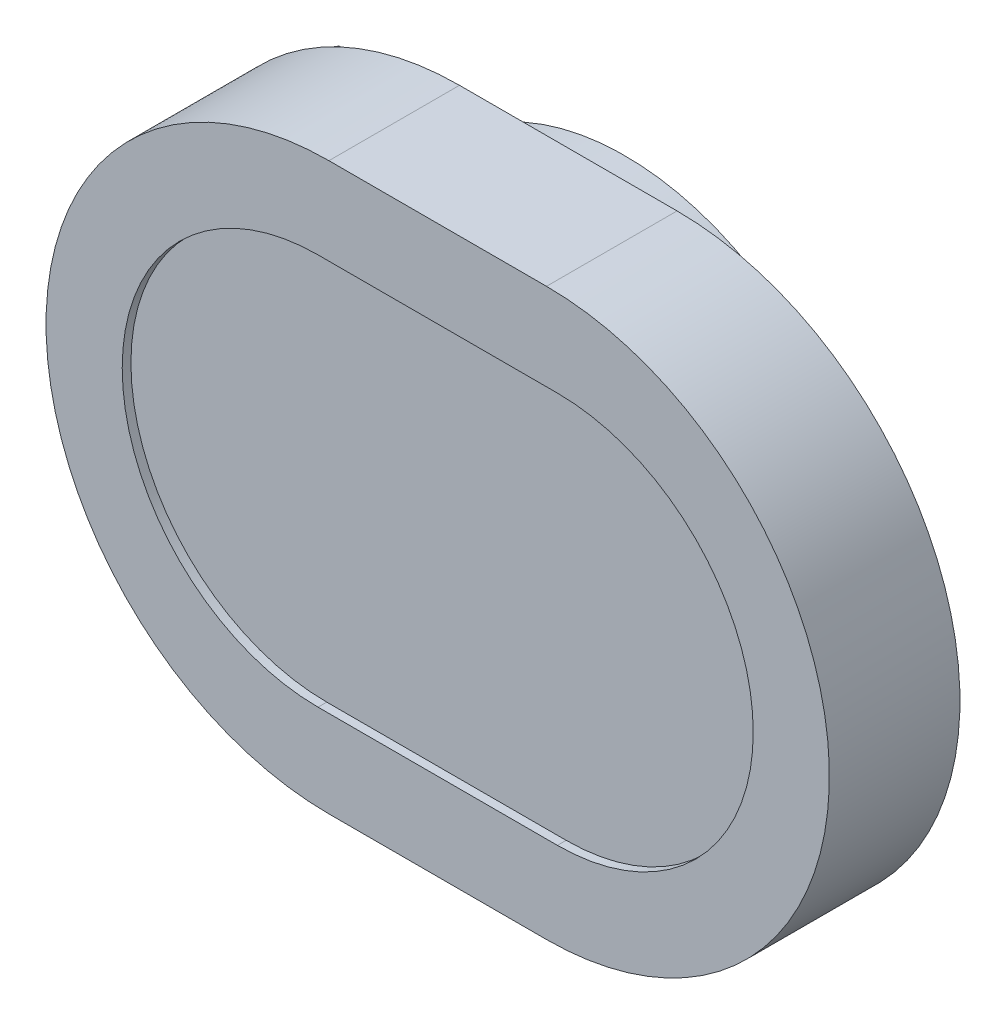
SolidWorks part; units mm, degrees
material "ABS"
ref_plane "Спереди" through (0, 0, 0) normal (0, 0, 1) x (1, 0, 0)
ref_plane "Сверху" through (0, 0, 0) normal (0, 1, 0) x (1, 0, 0)
ref_plane "Справа" through (0, 0, 0) normal (1, 0, 0) x (0, 0, -1)
ref_axis "Ось1" through (0, 0, 50) along (0, 0, -1)
sketch "Эскиз1" plane through (0, 0, 0) normal (0, 0, 1) x (1, 0, 0)
  circle A0 centre (0, 0) radius 5.7
  dimension "D1" = 11.4
extrude "Бобышка-Вытянуть1" add sketch "Эскиз1" along normal blind 1.3
sketch "Эскиз2" plane through (0, 0, 1.3) normal (0, 0, 1) x (1, 0, 0)
  line L0 (-2.5, 0) -> (2.5, 0) construction
  line L1 (-2.5, 6.5) -> (2.5, 6.5)
  line L2 (-2.5, -6.5) -> (2.5, -6.5)
  arc A0 (-2.5, 6.5) -> (-2.5, -6.5) centre (-2.5, 0) ccw
  arc A1 (2.5, -6.5) -> (2.5, 6.5) centre (2.5, 0) ccw
  point P2 (0, 0)
  point P8 (-9, 0)
  point P9 (9, 0)
  dimension "D1" = 18
  dimension "D2" = 13
extrude "Бобышка-Вытянуть2" add sketch "Эскиз2" along normal blind 2.8
sketch "Эскиз3" plane through (0, 0, 4.1) normal (0, 0, 1) x (1, 0, 0)
  line L0 (-2.75, 0) -> (2.75, 0) construction
  line L1 (-2.75, 4.5) -> (2.75, 4.5)
  line L2 (-2.75, -4.5) -> (2.75, -4.5)
  line L3 (-2.5, 0) -> (2.5, 0) construction
  line L4 (-2.5, 6.5) -> (2.5, 6.5)
  line L5 (-2.5, -6.5) -> (2.5, -6.5)
  line L6 (2.5, 6.5) -> (-2.5, 6.5) construction
  arc A0 (-2.75, 4.5) -> (-2.75, -4.5) centre (-2.75, 0) ccw
  arc A1 (2.75, -4.5) -> (2.75, 4.5) centre (2.75, 0) ccw
  arc A2 (-2.5, 6.5) -> (-2.5, -6.5) centre (-2.5, 0) ccw
  arc A3 (2.5, -6.5) -> (2.5, 6.5) centre (2.5, 0) ccw
  arc A4 (-2.5, 6.5) -> (-2.5, -6.5) centre (-2.5, 0) ccw construction
  point P2 (0, 0)
  point P8 (7.25, 0)
  point P9 (-7.25, 0)
  point P12 (0, 0)
  point P19 (0, 6.5)
  point P20 (0, 6.5)
  point P24 (-9, 0)
  point P25 (-9, 0)
  dimension "D1" = 9
  dimension "D2" = 14.5
extrude "Бобышка-Вытянуть3" add sketch "Эскиз3" along normal blind 0.2
sketch "Эскиз4" plane through (0, 0, 1.3) normal (0, 0, -1) x (-1, 0, 0)
  line L0 (5.3557, 2.5) -> (8.3319, 2.5)
  line L1 (5.6641, 5.5) -> (2.1641, 5.5)
  line L2 (5.3557, -2.5) -> (8.3319, -2.5)
  line L3 (5.6641, -5.5) -> (2.1641, -5.5)
  line L4 (5.3557, -2.5) -> (5.3557, 2.5) construction
  line L5 (0, 0) -> (5.3557, 0) construction
  line L6 (-2.5, 6.5) -> (2.5, 6.5) construction
  line L7 (5.6641, 5.5) -> (5.9641, 5.5) construction
  arc A0 (2.5, -6.5) -> (2.5, 6.5) centre (2.5, 0) ccw construction
  arc A5 (8.3319, 2.5) -> (5.6641, 5.5) centre (2.5, 0) ccw
  arc A6 (8.3319, -2.5) -> (5.6641, -5.5) centre (2.5, 0) cw
  arc A8 (2.1641, 5.5) -> (5.3557, 2.5) centre (0, 0) cw
  arc A9 (5.3557, -2.5) -> (2.1641, -5.5) centre (0, 0) cw
  circle A10 centre (0, 0) radius 5.7 construction
  dimension "D1" = 1
  dimension "D4" = 0.3
  dimension "D2" = 4
  dimension "D3" = 3.5
extrude "Бобышка-Вытянуть4" add sketch "Эскиз4" along normal blind 0.4
